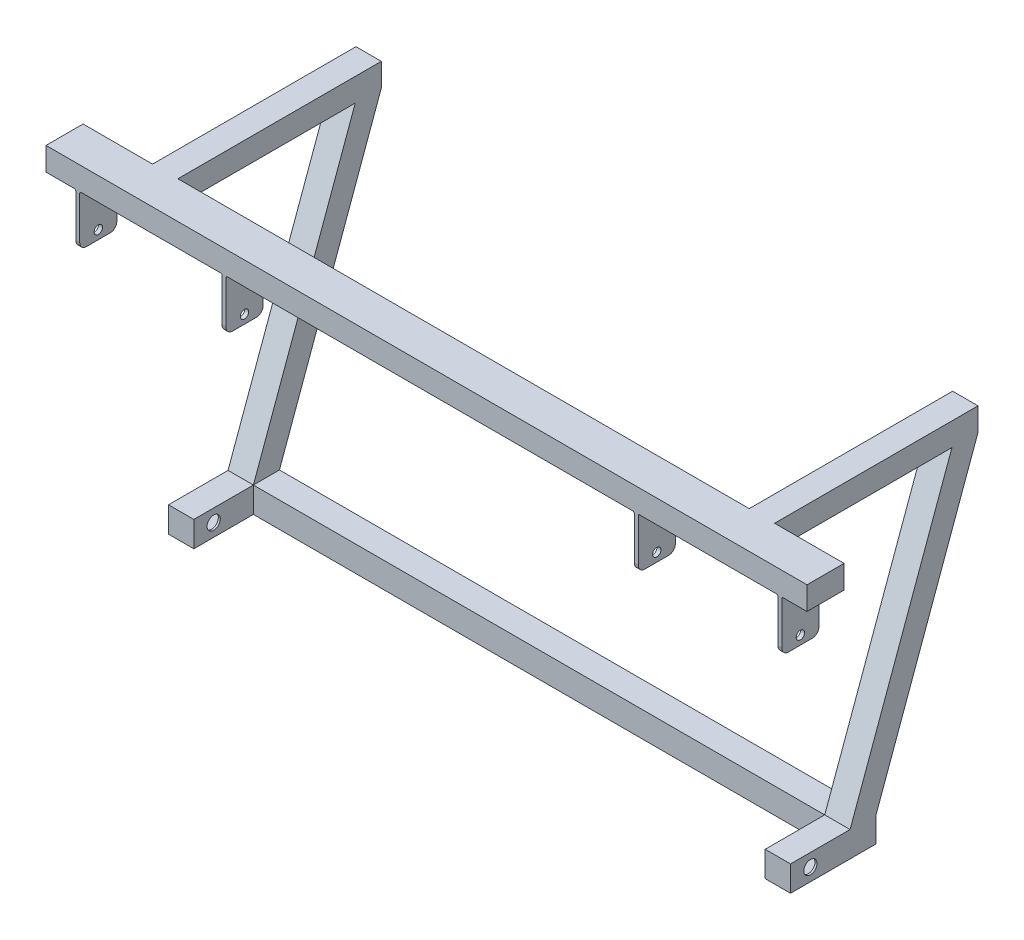
SolidWorks part; units mm, degrees
ref_plane "Front Plane" through (0, 0, 0) normal (0, 0, 1) x (1, 0, 0)
ref_plane "Top Plane" through (0, 0, 0) normal (0, 1, 0) x (1, 0, 0)
ref_plane "Right Plane" through (0, 0, 0) normal (1, 0, 0) x (0, 0, -1)
sketch "Sketch1" plane through (0, 0, 0) normal (0, 0, 1) x (1, 0, 0)
  line L1 (-575, -17.5) -> (575, -17.5)
  line L2 (-575, -17.5) -> (-575, 17.5)
  line L3 (-575, 17.5) -> (575, 17.5)
  line L4 (575, -17.5) -> (575, 17.5)
  line L5 (-575, -17.5) -> (575, 17.5) construction
  line L6 (-575, 17.5) -> (575, -17.5) construction
  point P0 (0, 0)
extrude "Boss-Extrude1" add sketch "Sketch1" along normal mid plane 56
sketch "Sketch4" plane through (0, 0, -28) normal (0, 0, -1) x (-1, 0, 0)
  line L0 (-575, 17.5) -> (-470, 17.5)
  line L1 (-575, 17.5) -> (575, 17.5) construction
  line L2 (575, -17.5) -> (-575, -17.5) construction
  line L3 (-470, 17.5) -> (-431.7, 17.5)
  line L4 (-470, 17.5) -> (-470, -17.5)
  line L5 (-470, -17.5) -> (-431.7, -17.5)
  line L6 (-431.7, 17.5) -> (-431.7, -17.5)
  line L7 (0, 199.87) -> (0, -199.87) construction
  line L8 (431.7, 17.5) -> (431.7, -17.5)
  line L9 (470, -17.5) -> (431.7, -17.5)
  line L10 (470, 17.5) -> (470, -17.5)
  line L11 (470, 17.5) -> (431.7, 17.5)
  line M6 (-575, -17.5) -> (575, -17.5)
  line M8 (575, 17.5) -> (-575, 17.5)
extrude "Boss-Extrude4" add sketch "Sketch4" along normal blind 307.4 contours L6 L4 M8 M6 | L10 L8 M8 M6 region at (450.85, 0, -28) region at (-450.85, 0, -28)
sketch "Sketch5" plane through (470, 0, 0) normal (1, 0, 0) x (0, 0, -1)
  line L0 (28, -17.5) -> (296, -17.5)
  line L1 (335.4, -17.5) -> (28, -17.5) construction
  line L2 (296, -17.5) -> (142.0909, -440.3617)
  line L3 (335.4, -17.5) -> (181.4909, -440.3617)
  line L4 (181.4909, -440.3617) -> (142.0909, -440.3617)
  line L5 (296, -17.5) -> (335.4, -17.5)
  line M7 (28, -17.5) -> (335.4, -17.5)
extrude "Boss-Extrude5" add sketch "Sketch5" against normal up to surface (38.3 mm away) contours L4 L3 L2 M7 region at (470, -228.9308, -238.7455) up to face at (431.7, 0, -181.7)
sketch "Sketch6" plane through (-431.7, 0, 0) normal (1, 0, 0) x (0, 0, -1)
  line L0 (28, -17.5) -> (296, -17.5)
  line L1 (335.4, -17.5) -> (28, -17.5) construction
  line L2 (296, -17.5) -> (142.0909, -440.3617)
  line L3 (335.4, -17.5) -> (181.4909, -440.3617)
  line L4 (181.4909, -440.3617) -> (142.0909, -440.3617)
  line L5 (296, -17.5) -> (335.4, -17.5)
  line M2 (28, -17.5) -> (335.4, -17.5)
extrude "Boss-Extrude6" add sketch "Sketch6" against normal up to surface (38.3 mm away) contours L4 L3 L2 M2 region at (-431.7, -228.9308, -238.7455) up to face at (-470, 0, -181.7)
sketch "Sketch7" plane through (0, -440.3617, 0) normal (0, -1, 0) x (1, 0, 0)
  line L1 (470, -142.0909) -> (431.7, -142.0909)
  line L2 (470, -142.0909) -> (470, -181.4909)
  line L3 (470, -181.4909) -> (431.7, -181.4909)
  line L4 (431.7, -142.0909) -> (431.7, -181.4909)
extrude "Boss-Extrude7" add sketch "Sketch7" along normal blind 38.5
sketch "Sketch8" plane through (431.7, 0, 0) normal (-1, 0, 0) x (0, 0, 1)
  line L1 (-142.0909, -440.3617) -> (-181.4909, -440.3617)
  line L2 (-142.0909, -440.3617) -> (-142.0909, -478.8617)
  line L3 (-142.0909, -478.8617) -> (-181.4909, -478.8617)
  line L4 (-181.4909, -440.3617) -> (-181.4909, -478.8617)
extrude "Boss-Extrude8" add sketch "Sketch8" along normal up to surface (901.7 mm away) up to face at (-470, -128.3176, -192.3403)
sketch "Sketch9" plane through (0, 0, -142.0909) normal (0, 0, 1) x (1, 0, 0)
  line L0 (0, -199.87) -> (0, 199.87) construction
  line L1 (-431.7, -440.3617) -> (-470, -440.3617)
  line L2 (-431.7, -440.3617) -> (-431.7, -478.8617)
  line L3 (-431.7, -478.8617) -> (-470, -478.8617)
  line L4 (-470, -440.3617) -> (-470, -478.8617)
  line L5 (470, -440.3617) -> (470, -478.8617)
  line L6 (431.7, -478.8617) -> (470, -478.8617)
  line L7 (431.7, -440.3617) -> (431.7, -478.8617)
  line L8 (431.7, -440.3617) -> (470, -440.3617)
extrude "Boss-Extrude9" add sketch "Sketch9" along normal blind 90 contours L2 L1 L4 L3 | L5 L6 L7 L8
sketch "Sketch10" plane through (0, 0, 28) normal (0, 0, 1) x (1, 0, 0)
  line L0 (-575, -17.5) -> (-530, -17.5)
  line L1 (-575, -17.5) -> (575, -17.5) construction
  line L2 (-530, -17.5) -> (-530, -94.5)
  line L3 (-530, -94.5) -> (-524, -94.5)
  line L4 (-524, -94.5) -> (-524, -17.5)
  line L5 (-524, -17.5) -> (-309, -17.5)
  line L6 (-309, -17.5) -> (-309, -94.5)
  line L7 (-309, -94.5) -> (-303, -94.5)
  line L8 (-303, -94.5) -> (-303, -17.5)
  line L9 (-303, -17.5) -> (314, -17.5)
  line L10 (314, -17.5) -> (314, -94.5)
  line L11 (314, -94.5) -> (320, -94.5)
  line L12 (320, -94.5) -> (320, -17.5)
  line L13 (320, -17.5) -> (531, -17.5)
  line L14 (531, -17.5) -> (531, -94.5)
  line L15 (531, -94.5) -> (537, -94.5)
  line L16 (537, -94.5) -> (537, -17.5)
  line L17 (537, -17.5) -> (575, -17.5)
  line L18 (-530, -17.5) -> (-524, -17.5)
  line L19 (-309, -17.5) -> (-303, -17.5)
  line L20 (-530, -17.5) -> (-524, -17.5)
  line L21 (-309, -17.5) -> (-303, -17.5)
  line L22 (314, -17.5) -> (320, -17.5)
  line L23 (531, -17.5) -> (537, -17.5)
  line L24 (531, -17.5) -> (537, -17.5)
  line L25 (314, -17.5) -> (320, -17.5)
  line L26 (-309, -17.5) -> (-303, -17.5)
sketch "Sketch11" plane through (0, -17.5, 0) normal (0, -1, 0) x (1, 0, 0)
  line L0 (-530, 28) -> (-524, 28) construction
  line L1 (-530, 28) -> (-524, 28)
  line L2 (-530, 28) -> (-530, -28)
  line L3 (-530, -28) -> (-524, -28)
  line L4 (-524, 28) -> (-524, -28)
  line L5 (-530, 28) -> (-524, 28) construction
  line L6 (-575, -28) -> (-470, -28) construction
  line L7 (-309, 28) -> (-303, 28) construction
  line L8 (-309, 28) -> (-303, 28)
  line L9 (-309, 28) -> (-309, -28)
  line L10 (-309, -28) -> (-303, -28)
  line L11 (-303, 28) -> (-303, -28)
  line L12 (-309, 28) -> (-303, 28) construction
  line L13 (-431.7, -28) -> (431.7, -28) construction
  line L14 (314, 28) -> (320, 28) construction
  line L15 (314, 28) -> (320, 28)
  line L16 (314, 28) -> (314, -28)
  line L17 (314, -28) -> (320, -28)
  line L18 (320, 28) -> (320, -28)
  line L19 (314, 28) -> (320, 28) construction
  line L20 (531, 28) -> (537, 28) construction
  line L21 (531, 28) -> (537, 28)
  line L22 (531, 28) -> (531, -28)
  line L23 (531, -28) -> (537, -28)
  line L24 (537, 28) -> (537, -28)
  line L25 (531, 28) -> (537, 28) construction
  line L26 (470, -28) -> (575, -28) construction
extrude "Boss-Extrude10" add sketch "Sketch11" along normal blind 77 contours L2 L1 L4 L3 | L9 L8 L11 L10 | L22 L21 L24 L23 | L16 L15 L18 L17
fillet "Fillet1" radius 10 8 edges at (534, -94.5, 28) (534, -94.5, -28) (317, -94.5, -28) (317, -94.5, 28) (-306, -94.5, 28) (-306, -94.5, -28) (-527, -94.5, 28) (-527, -94.5, -28)
sketch "Sketch12" plane through (-530, 0, 0) normal (-1, 0, 0) x (0, 0, 1)
  line L0 (0, -94.5) -> (0, -81.3)
  line L1 (18, -94.5) -> (-18, -94.5) construction
  circle A0 centre (0, -81.3) radius 6.3
extrude "Cut-Extrude1" cut sketch "Sketch12" against normal up to surface (1067 mm away) contours A0 up to face at (537, -66.1904, 0)
sketch "Sketch13" [suppressed] plane through (0, 0, -335.4) normal (0, 0, -1) x (-1, 0, 0)
  line L0 (-470, 17.5) -> (-431.7, -17.5)
  line L3 (-464, -11.5) -> (-437.7, -11.5)
  line L4 (-464, -11.5) -> (-464, 11.5)
  line L5 (-464, 11.5) -> (-437.7, 11.5)
  line L6 (-437.7, -11.5) -> (-437.7, 11.5)
  line L7 (-464, -11.5) -> (-437.7, 11.5) construction
  line L8 (-464, 11.5) -> (-437.7, -11.5) construction
  line L10 (0, 199.87) -> (0, -199.87) construction
  line L11 (437.7, -11.5) -> (437.7, 11.5)
  line L12 (464, 11.5) -> (437.7, 11.5)
  line L13 (464, -11.5) -> (464, 11.5)
  line L14 (464, -11.5) -> (437.7, -11.5)
  point P6 (-450.85, 0)
  point P15 (450.85, 0)
shell "Shell1" thickness 3 removed face at (575, 0, 0)
sketch "Sketch17" plane through (0, 14.5, 0) normal (0, -1, 0) x (1, 0, 0)
  line L0 (575, -25) -> (467, -25) construction
  line L1 (575, 25) -> (572, 25)
  line L2 (575, 25) -> (575, -25)
  line L3 (575, -25) -> (572, -25)
  line L4 (572, 25) -> (572, -25)
extrude "Boss-Extrude12" add sketch "Sketch17" along normal up to surface (29 mm away)
fillet "Fillet2" radius 2 8 edges at (537, -17.5, 0) (531, -17.5, 0) (314, -17.5, 0) (320, -17.5, 0) (-303, -17.5, 0) (-309, -17.5, 0) (-524, -17.5, 0) (-530, -17.5, 0)
sketch "Sketch18" plane through (470, 0, 0) normal (1, 0, 0) x (0, 0, -1)
  circle A0 centre (82.0909, -459.6117) radius 10
extrude "Cut-Extrude2" cut sketch "Sketch18" against normal up to surface (940 mm away) up to face at (-470, -229.6308, -163.2055)
